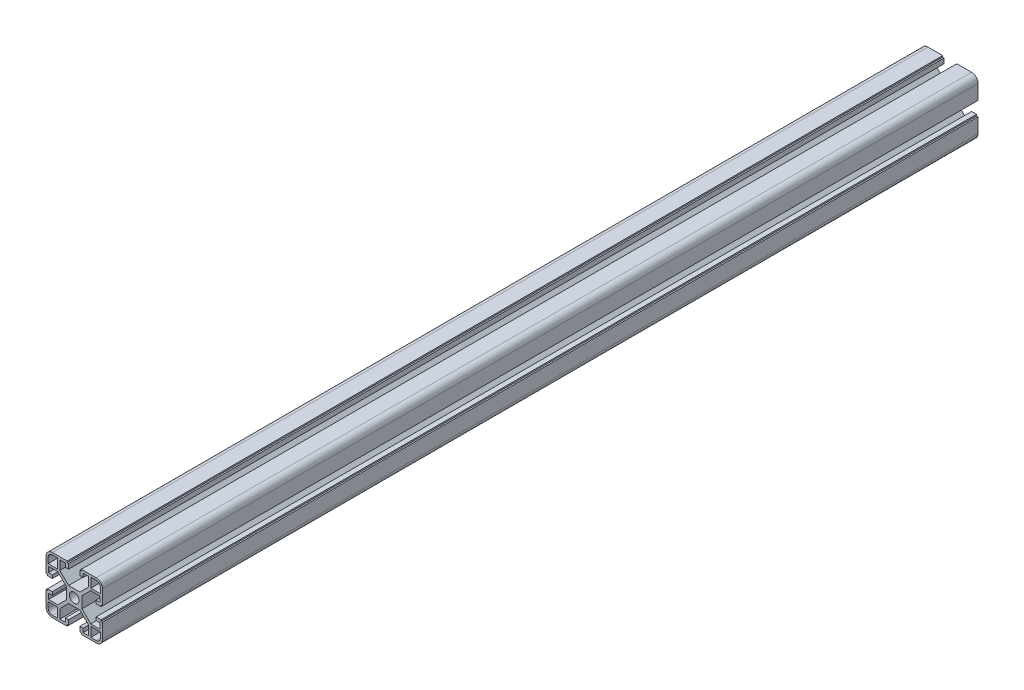
SolidWorks part; units mm, degrees
material "6061-T6 (SS)"
ref_plane "Front Plane" through (0, 0, 0) normal (0, 0, 1) x (1, 0, 0)
ref_plane "Top Plane" through (0, 0, 0) normal (0, 1, 0) x (1, 0, 0)
ref_plane "Right Plane" through (0, 0, 0) normal (1, 0, 0) x (0, 0, -1)
sketch "Sketch1" plane through (0, 0, 0) normal (0, 0, 1) x (1, 0, 0)
  line L0 (3.4, 0) -> (5.5, 0)
  line L1 (10.19, 11.69) -> (4, 5.5)
  line L2 (11.69, 10.19) -> (5.5, 4)
  line L3 (18.2, 10.19) -> (11.69, 10.19)
  line L4 (18.2, 10.19) -> (18.2, 6.3)
  line L5 (18.2, 6.3) -> (15.5, 6.3)
  line L6 (15.5, 6.3) -> (15.5, 4)
  line L7 (15.5, 4) -> (19, 4)
  line L8 (19, 4) -> (19, 5)
  line L9 (19, 5) -> (20, 5)
  line L10 (20, 5) -> (20, 15.5)
  line L11 (15.5, 20) -> (5, 20)
  line L12 (18.5, 11.69) -> (18.5, 15.5)
  line L13 (15.5, 18.5) -> (11.69, 18.5)
  line L14 (11.69, 11.69) -> (11.69, 18.5)
  line L15 (0, 3.4) -> (0, 5.5)
  line L16 (4, 5.5) -> (0, 5.5)
  line L17 (5, 20) -> (5, 19)
  line L18 (5.5, 0) -> (5.5, 4)
  line L19 (5, 19) -> (4, 19)
  line L20 (4, 19) -> (4, 15.5)
  line L21 (4, 15.5) -> (6.3, 15.5)
  line L22 (10.19, 11.69) -> (10.19, 18.2)
  line L23 (11.69, 11.69) -> (18.5, 11.69)
  line L24 (6.3, 18.2) -> (6.3, 15.5)
  line L25 (10.19, 18.2) -> (6.3, 18.2)
  arc A0 (20, 15.5) -> (15.5, 20) centre (15.5, 15.5) ccw
  arc A1 (18.5, 15.5) -> (15.5, 18.5) centre (15.5, 15.5) ccw
  arc A2 (3.4, 0) -> (0, 3.4) centre (0, 0) ccw
  point P4 (0, 4.45)
  dimension "D3" = 4.5
  dimension "D18" = 1.5
  dimension "D9" = 3.4
  dimension "D20" = 1.8
  dimension "D25" = 3
  dimension "D1" = 5.5
  dimension "D2" = 1.5
  dimension "D4" = 14.5
  dimension "D5" = 1.5
  dimension "D6" = 2.1
  dimension "D7" = 2.3
  dimension "D8" = 1.8
  dimension "D10" = 6.81
  dimension "D11" = 2.1
  dimension "D12" = 1
  dimension "D13" = 4.5
  dimension "D14" = 45
  dimension "D15" = 14.5
  dimension "D16" = 1
  dimension "D17" = 1.5
  dimension "D19" = 6.81
  dimension "D21" = 4.5
  dimension "D22" = 2.3
  dimension "D23" = 1
  dimension "D24" = 1
  dimension "D26" = 8.754
  dimension "D27" = 8.754
  dimension "D28" = 4
  dimension "D29" = 4
extrude "Boss-Extrude1" add sketch "Sketch1" along normal blind 620
mirror "Mirror1" about plane through (0, 0, 0) normal (0, 1, 0) of "Boss-Extrude1"
mirror "Mirror2" about plane through (0, 0, 0) normal (1, 0, 0) of "Boss-Extrude1"
mirror "Mirror3" about plane through (0, 0, 0) normal (0, 1, 0) of "Mirror2"
